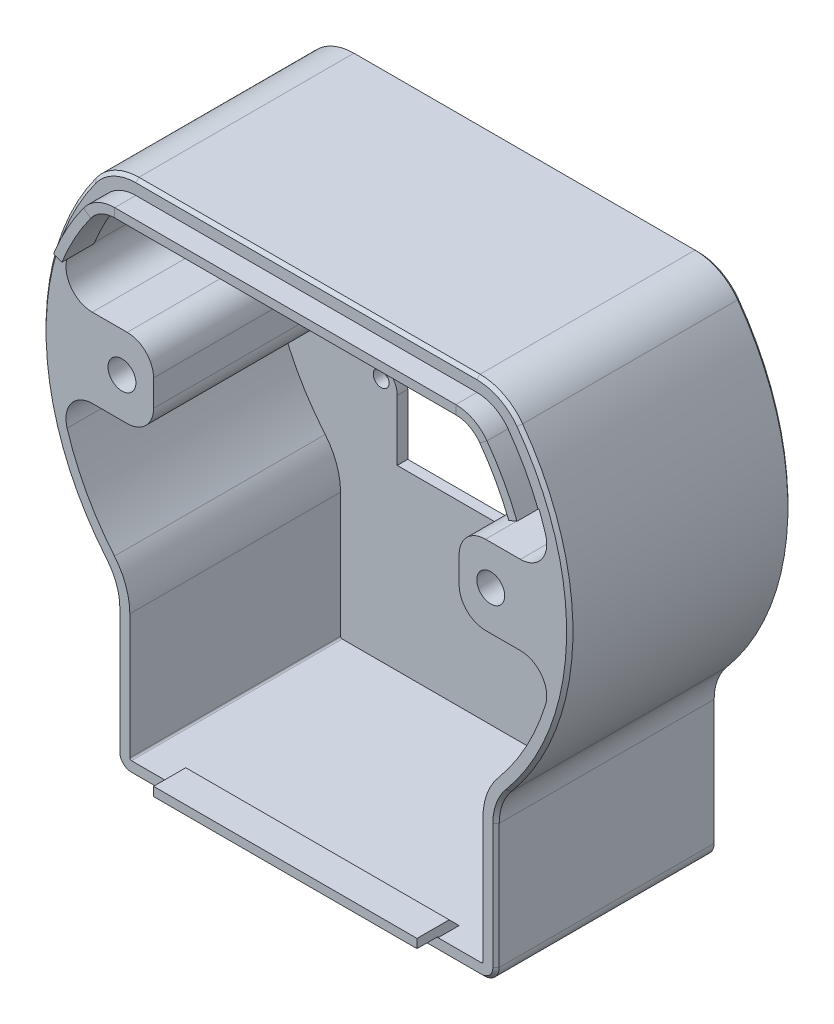
SolidWorks part; units mm, degrees
ref_plane "Ebene vorne" through (0, 0, 0) normal (0, 0, 1) x (1, 0, 0)
ref_plane "Ebene oben" through (0, 0, 0) normal (0, 1, 0) x (1, 0, 0)
ref_plane "Ebene rechts" through (0, 0, 0) normal (1, 0, 0) x (0, 0, -1)
sketch "Skizze1" plane through (0, 0, 0) normal (0, 0, 1) x (1, 0, 0)
  line L0 (0, 15.499) -> (0, -28.3741) construction
  line L1 (0, 33.5) -> (-32.369, 33.5)
  line L2 (0, 33.5) -> (32.369, 33.5)
  line L3 (-36, -38.5227) -> (-36, -62.2)
  line L4 (-33.2, -65) -> (0, -65)
  line L5 (-50, 78.1636) -> (-50, -33.9451) construction
  line L6 (50, 78.1636) -> (50, -33.9451) construction
  line L7 (-50, 0) -> (50, 0) construction
  line L8 (36, -38.5227) -> (36, -62.2)
  line L10 (0, -65) -> (33.2, -65)
  arc A0 (-40.4612, 29.375) -> (-38.3333, -32.1023) centre (0, 0) ccw
  arc A3 (40.4612, 29.375) -> (38.3333, -32.1023) centre (0, 0) cw
  arc A8 (32.369, 33.5) -> (40.4612, 29.375) centre (32.369, 23.5) cw
  arc A9 (-32.369, 33.5) -> (-40.4612, 29.375) centre (-32.369, 23.5) ccw
  arc A10 (38.3333, -32.1023) -> (36, -38.5227) centre (46, -38.5227) ccw
  arc A11 (-38.3333, -32.1023) -> (-36, -38.5227) centre (-46, -38.5227) cw
  arc A12 (36, -62.2) -> (33.2, -65) centre (33.2, -62.2) cw
  arc A13 (-36, -62.2) -> (-33.2, -65) centre (-33.2, -62.2) ccw
  point P18 (0, 0)
  point P34 (36, -65)
  point P37 (-36, -65)
  dimension "D1" = 72
  dimension "D4" = 10
  dimension "D2" = 10
  dimension "D7" = 2.8
  dimension "D3" = 65
  dimension "D5" = 33.5
  dimension "D6" = 100
extrude "Linear-Austragen-Dünn1" add sketch "Skizze1" along normal blind 40 thin thin type one direction reverse wall 2.49
sketch "Skizze3" plane through (0, 0, 0) normal (0, 0, -1) x (-1, 0, 0)
  line L0 (36, -38.5227) -> (36, -62.2) construction
  line L1 (33.2, -65) -> (-33.2, -65) construction
  line L2 (-36, -62.2) -> (-36, -38.5227) construction
  line L3 (-32.369, 33.5) -> (32.369, 33.5) construction
  line L4 (36, -38.5227) -> (36, -62.2)
  line L5 (33.2, -65) -> (-33.2, -65)
  line L6 (-36, -62.2) -> (-36, -38.5227)
  line L7 (-32.369, 33.5) -> (32.369, 33.5)
  line L8 (-28.75, 13.25) -> (-26.75, 13.25)
  line L9 (-28.75, -28.75) -> (28.75, -28.75) construction
  line L10 (-28.75, -28.75) -> (-28.75, 28.75) construction
  line L11 (-28.75, 28.75) -> (28.75, 28.75) construction
  line L12 (28.75, -28.75) -> (28.75, 28.75) construction
  line L13 (-28.75, -28.75) -> (28.75, 28.75) construction
  line L14 (-28.75, 28.75) -> (28.75, -28.75) construction
  line L15 (-22.75, 17.25) -> (-22.75, 28.75)
  line L16 (0, 28.75) -> (0, -28.75) construction
  line L17 (28.75, 13.25) -> (26.75, 13.25)
  line L18 (22.75, 17.25) -> (22.75, 28.75)
  line L19 (-28.75, 0) -> (28.75, 0) construction
  line L20 (28.75, -13.25) -> (26.75, -13.25)
  line L21 (22.75, -17.25) -> (22.75, -28.75)
  line L22 (-28.75, -13.25) -> (-26.75, -13.25)
  line L23 (-22.75, -17.25) -> (-22.75, -28.75)
  line L24 (-28.75, 13.25) -> (-28.75, -13.25)
  line L25 (-22.75, -28.75) -> (22.75, -28.75)
  line L26 (28.75, -13.25) -> (28.75, 13.25)
  line L27 (22.75, 28.75) -> (-22.75, 28.75)
  arc A0 (38.3333, -32.1023) -> (36, -38.5227) centre (46, -38.5227) ccw construction
  arc A1 (33.2, -65) -> (36, -62.2) centre (33.2, -62.2) ccw construction
  arc A2 (-36, -62.2) -> (-33.2, -65) centre (-33.2, -62.2) ccw construction
  arc A3 (-36, -38.5227) -> (-38.3333, -32.1023) centre (-46, -38.5227) ccw construction
  arc A4 (-40.4612, 29.375) -> (-38.3333, -32.1023) centre (0, 0) ccw construction
  arc A5 (-32.369, 33.5) -> (-40.4612, 29.375) centre (-32.369, 23.5) ccw construction
  arc A6 (40.4612, 29.375) -> (32.369, 33.5) centre (32.369, 23.5) ccw construction
  arc A7 (38.3333, -32.1023) -> (40.4612, 29.375) centre (0, 0) ccw construction
  arc A8 (38.3333, -32.1023) -> (36, -38.5227) centre (46, -38.5227) ccw
  arc A9 (33.2, -65) -> (36, -62.2) centre (33.2, -62.2) ccw
  arc A10 (-36, -62.2) -> (-33.2, -65) centre (-33.2, -62.2) ccw
  arc A11 (-36, -38.5227) -> (-38.3333, -32.1023) centre (-46, -38.5227) ccw
  arc A12 (-40.4612, 29.375) -> (-38.3333, -32.1023) centre (0, 0) ccw
  arc A13 (-32.369, 33.5) -> (-40.4612, 29.375) centre (-32.369, 23.5) ccw
  arc A14 (40.4612, 29.375) -> (32.369, 33.5) centre (32.369, 23.5) ccw
  arc A15 (38.3333, -32.1023) -> (40.4612, 29.375) centre (0, 0) ccw
  arc A16 (-26.75, 13.25) -> (-22.75, 17.25) centre (-26.75, 17.25) ccw
  arc A17 (26.75, 13.25) -> (22.75, 17.25) centre (26.75, 17.25) cw
  arc A18 (26.75, -13.25) -> (22.75, -17.25) centre (26.75, -17.25) ccw
  arc A19 (-26.75, -13.25) -> (-22.75, -17.25) centre (-26.75, -17.25) cw
  dimension "D2" = 15.5
  dimension "D4" = 4
  dimension "D1" = 57.5
  dimension "D3" = 2
extrude "Aufsatz-Linear austragen2" add sketch "Skizze3" along normal blind 2
sketch "Skizze4" plane through (0, 0, -2) normal (0, 0, -1) x (-1, 0, 0)
  line L0 (0, 28.75) -> (0, -28.75) construction
  line L1 (22.75, 28.75) -> (-22.75, 28.75) construction
  line L2 (-22.75, -28.75) -> (22.75, -28.75) construction
  line L3 (-28.75, 0) -> (28.75, 0) construction
  line L4 (-28.75, 13.25) -> (-28.75, -13.25) construction
  line L5 (28.75, -13.25) -> (28.75, 13.25) construction
  circle A4 centre (-25.8, 16) radius 1.5
  circle A5 centre (25.8, 16) radius 1.5
  circle A6 centre (25.8, -16) radius 1.5
  circle A7 centre (-25.8, -16) radius 1.5
  dimension "D1" = 3
  dimension "D2" = 32
  dimension "D3" = 51.6
extrude "Schnitt-Linear austragen1" cut sketch "Skizze4" against normal up to next
sketch "Skizze6" plane through (0, 0, 0) normal (1, 0, 0) x (0, 0, -1)
  line L0 (0, -13.25) -> (0, 13.25) construction
  line L1 (0, -7.5) -> (-40, -7.5)
  line L2 (0, -7.5) -> (0, 7.5)
  line L3 (0, 7.5) -> (-40, 7.5)
  line L4 (-40, -7.5) -> (-40, 7.5)
  line L5 (-40, 27.9121) -> (-40, -30.5036) construction
  point P8 (0, 0)
  dimension "D1" = 15
extrude "Aufsatz-Linear austragen3" add sketch "Skizze6" along normal up to next from offset 29
extrude "Aufsatz-Linear austragen4" add sketch "Skizze6<2>" against normal up to next from offset 29 offset against normal yes
sketch "Skizze6<2>" plane through (0, 0, 0) normal (1, 0, 0) x (0, 0, -1) same geometry as "Skizze6"
sketch "Skizze7" plane through (0, 0, 40) normal (0, 0, 1) x (1, 0, 0)
  line L0 (0, 33.5) -> (0, -65) construction
  line L1 (32.369, 33.5) -> (-32.369, 33.5) construction
  line L2 (-33.2, -65) -> (33.2, -65) construction
  circle A0 centre (-35, 0) radius 2.65
  circle A1 centre (35, 0) radius 2.65
  dimension "D1" = 70
  dimension "D2" = 5.3
extrude "Schnitt-Linear austragen2" cut sketch "Skizze7" against normal up to next
sketch "Skizze8" plane through (0, 0, 40) normal (0, 0, 1) x (1, 0, 0)
  circle A0 centre (-35, 0) radius 4.5
  circle A1 centre (35, 0) radius 4.5
  dimension "D1" = 9
extrude "Schnitt-Linear austragen3" cut sketch "Skizze8" against normal up to next from offset 5 offset against normal yes
sketch "Skizze9" plane through (0, 0, 0) normal (1, 0, 0) x (0, 0, -1)
  line L0 (-40, 31.01) -> (-40, 30.81)
  line L1 (-40, 31.01) -> (-40, 27.9121) construction
  line L2 (-40, 30.81) -> (-44, 30.81)
  line L3 (-44, 30.81) -> (-44, 29.12)
  line L4 (-44, 29.12) -> (-37.89, 29.12)
  line L5 (-37.89, 29.12) -> (-35, 32.01)
  line L6 (-40, 31.01) -> (0, 31.01) construction
  line L8 (-20, 31.01) -> (-20, -62.51) construction
  line L9 (-40, -62.51) -> (0, -62.51) construction
  line L10 (-20, -15.75) -> (-40, -15.75) construction
  line L11 (-40, -7.5) -> (-40, -30.5036) construction
  line L18 (-40, 31.01) -> (-40, 32.01)
  line L19 (-40, 33.5) -> (-40, 29.375) construction
  line L20 (-40, 32.01) -> (-35, 32.01)
  line L21 (-40, -63.51) -> (-35, -63.51)
  line L22 (-40, -62.51) -> (-40, -63.51)
  line L23 (-37.89, -60.62) -> (-35, -63.51)
  line L24 (-44, -60.62) -> (-37.89, -60.62)
  line L25 (-44, -62.31) -> (-44, -60.62)
  line L26 (-40, -62.31) -> (-44, -62.31)
  line L27 (-40, -62.51) -> (-40, -62.31)
  dimension "D1" = 0.2
  dimension "D2" = 1.69
  dimension "D3" = 1
  dimension "D4" = 5
  dimension "D5" = 4
  dimension "D6" = 45
sketch "Skizze10" plane through (0, 0, 40) normal (0, 0, 1) x (1, 0, 0)
  line L2 (-46.8375, 17.5) -> (46.8375, 17.5) construction
  line L3 (-46.9143, 7.5) -> (-29, 7.5) construction
  line L4 (0, 33.5) -> (0, -62.51) construction
  line L5 (32.369, 33.5) -> (-32.369, 33.5) construction
  line L6 (-33.2, -62.51) -> (33.2, -62.51) construction
  line L7 (32.369, 31.01) -> (-32.369, 31.01) construction
  line L8 (32.369, 31.01) -> (-32.369, 31.01)
  line L9 (33.51, -62.2) -> (33.51, -38.5227) construction
  line L10 (-33.51, -38.5227) -> (-33.51, -62.2) construction
  line L11 (-33.2, -62.51) -> (33.2, -62.51) construction
  line L12 (33.51, -62.2) -> (33.51, -38.5227)
  line L13 (-33.51, -38.5227) -> (-33.51, -62.2)
  line L14 (-33.2, -62.51) -> (33.2, -62.51)
  arc A2 (38.4462, 27.9121) -> (32.369, 31.01) centre (32.369, 23.5) ccw construction
  arc A4 (46.9143, 7.5) -> (38.4462, 27.9121) centre (0, 0) ccw construction
  arc A6 (-38.4462, 27.9121) -> (-46.9143, 7.5) centre (0, 0) ccw construction
  arc A8 (38.3333, -32.1023) -> (40.4612, 29.375) centre (0, 0) ccw construction
  arc A9 (-40.4612, 29.375) -> (-38.3333, -32.1023) centre (0, 0) ccw construction
  arc A10 (-32.369, 31.01) -> (-38.4462, 27.9121) centre (-32.369, 23.5) ccw construction
  arc A11 (38.4462, 27.9121) -> (32.369, 31.01) centre (32.369, 23.5) ccw
  arc A12 (44.1696, 17.5) -> (38.4462, 27.9121) centre (0, 0) ccw
  arc A13 (-38.4462, 27.9121) -> (-44.1696, 17.5) centre (0, 0) ccw
  arc A14 (-32.369, 31.01) -> (-38.4462, 27.9121) centre (-32.369, 23.5) ccw
  arc A15 (33.2, -62.51) -> (33.51, -62.2) centre (33.2, -62.2) ccw construction
  arc A16 (-33.51, -62.2) -> (-33.2, -62.51) centre (-33.2, -62.2) ccw construction
  arc A17 (33.2, -62.51) -> (33.51, -62.2) centre (33.2, -62.2) ccw
  arc A18 (-33.51, -62.2) -> (-33.2, -62.51) centre (-33.2, -62.2) ccw
  dimension "D1" = 10
sweep "Austragung12" add profiles "Skizze9" path "Skizze10"
extrude "Aufsatz-Linear austragen6" add sketch "Skizze9<4>" along normal mid plane 50 contours L23 L21 L22 L27 L26 L25 L24
sketch "Skizze9<4>" plane through (0, 0, 0) normal (1, 0, 0) x (0, 0, -1) same geometry as "Skizze9"
fillet "Verrundung1" radius 5 8 edges at (29, 7.5, 20) (29, -7.5, 20) (-29, -7.5, 20) (-29, 7.5, 20) (46.9143, 7.5, 20) (46.9143, -7.5, 20) (-46.9143, -7.5, 20) (-46.9143, 7.5, 20)
chamfer "Fase2" distance 0.6 angle 45 26 edges at (36, -50.3614, -2) (35.1799, -64.1799, -2) (36.6014, -35.1071, -2) (0, -65, -2) (49.9701, -1.7296, -2) (-35.1799, -64.1799, -2) (36.9104, 32.4093, -2) (-36, -50.3614, -2) (0, 33.5, -2) (-36.6014, -35.1071, -2) (-36.9104, 32.4093, -2) (-49.9701, -1.7296, -2) (36, -50.3614, 40) (36.6014, -35.1071, 40) (35.1799, -64.1799, 40) (49.9701, -1.7296, 40) (0, -65, 40) (36.9104, 32.4093, 40) (-35.1799, -64.1799, 40) (0, 33.5, 40) (-36, -50.3614, 40) (-36.9104, 32.4093, 40) (-36.6014, -35.1071, 40) (-49.9701, -1.7296, 40) (-39.5, 0, -2) (30.5, 0, -2)
